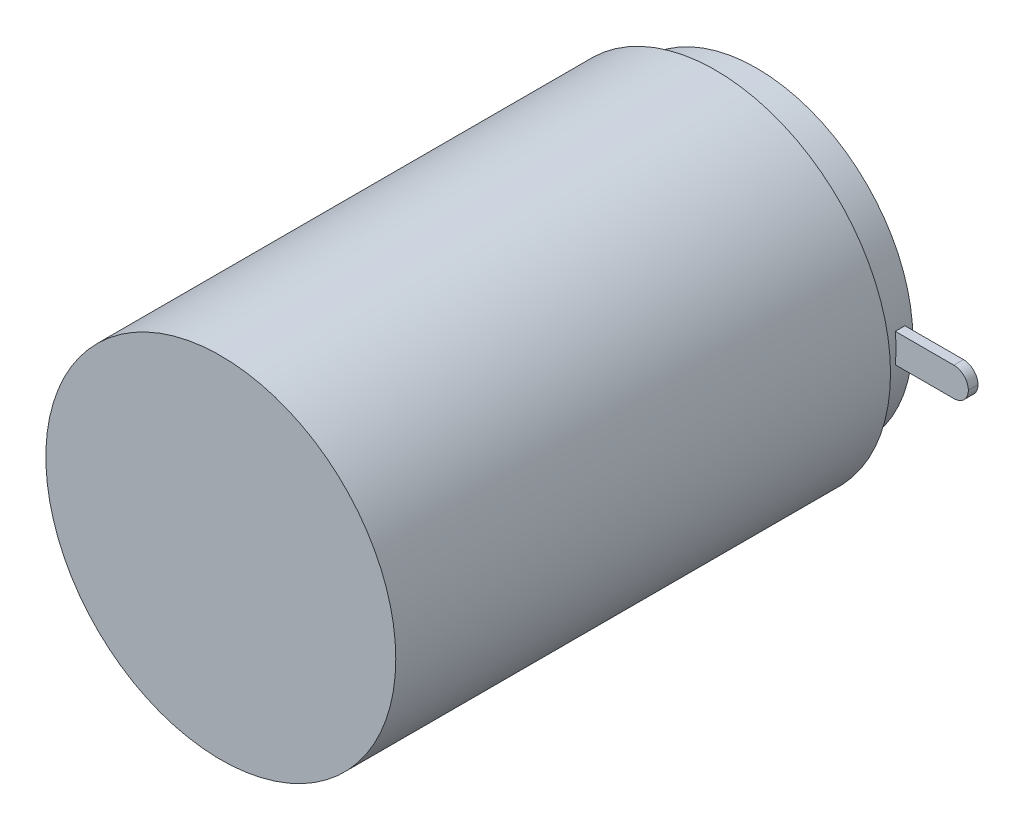
SolidWorks part; units mm, degrees
ref_plane "Plan de face" through (0, 0, 0) normal (0, 0, 1) x (1, 0, 0)
ref_plane "Plan de dessus" through (0, 0, 0) normal (0, 1, 0) x (1, 0, 0)
ref_plane "Plan de droite" through (0, 0, 0) normal (1, 0, 0) x (0, 0, -1)
sketch "Esquisse1" plane through (0, 0, 0) normal (0, 0, 1) x (1, 0, 0)
  circle A0 centre (0, 0) radius 14.5
  dimension "D1" = 29
extrude "Boss.-Extru.1" add sketch "Esquisse1" along normal blind 41
sketch "Esquisse2" plane through (0, 0, 0) normal (0, 0, -1) x (-1, 0, 0)
  circle A0 centre (0, 0) radius 12.95
extrude "Boss.-Extru.2" add sketch "Esquisse2" along normal blind 3.4
ref_plane "Plan2" through (12.95, 0, 0) normal (1, 0, 0) x (0, 0, -1)
sketch "Esquisse3" plane through (12.95, 0, 0) normal (1, 0, 0) x (0, 0, -1)
  line L1 (2.8, 1.2) -> (2, 1.2)
  line L2 (2.8, 1.2) -> (2.8, -1.2)
  line L3 (2.8, -1.2) -> (2, -1.2)
  line L4 (2, 1.2) -> (2, -1.2)
  dimension "D1" = 2
  dimension "D2" = 0.8
  dimension "D3" = 1.2
  dimension "D4" = 2.4
extrude "Boss.-Extru.3" add sketch "Esquisse3" along normal blind 6 and the other way blind 1
ref_plane "Plan3" through (-12.95, 0, 0) normal (-1, 0, 0) x (0, 0, 1)
sketch "Esquisse4" plane through (-12.95, 0, 0) normal (-1, 0, 0) x (0, 0, 1)
  line L1 (-2, 1.2) -> (-2.8, 1.2)
  line L2 (-2, 1.2) -> (-2, -1.2)
  line L3 (-2, -1.2) -> (-2.8, -1.2)
  line L4 (-2.8, 1.2) -> (-2.8, -1.2)
  dimension "D1" = 2.4
  dimension "D2" = 1.2
  dimension "D3" = 0.8
  dimension "D4" = 2
extrude "Boss.-Extru.4" add sketch "Esquisse4" along normal blind 6 and the other way blind 1
fillet "Congé1" radius 1.2 4 edges at (18.95, -1.2, -2.4) (18.95, 1.2, -2.4) (-18.95, -1.2, -2.4) (-18.95, 1.2, -2.4)
